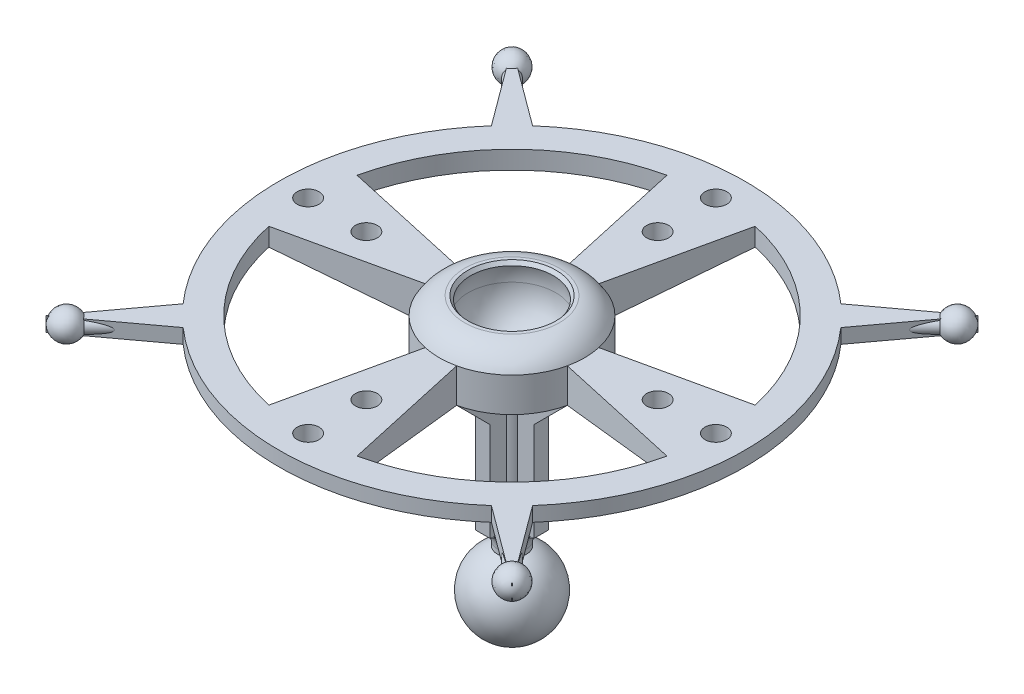
SolidWorks part; units mm, degrees
other "Markup1"
sketch "Sketch8" plane through (-15, -13.5, -15) normal (-0.6433, -0.4106, -0.6463) x (0.1908, 0.7315, -0.6546)
ref_plane "Front Plane" through (0, 0, 0) normal (0, 0, 1) x (1, 0, 0)
ref_plane "Top Plane" through (0, 0, 0) normal (0, 1, 0) x (1, 0, 0)
ref_plane "Right Plane" through (0, 0, 0) normal (1, 0, 0) x (0, 0, -1)
sketch "Sketch1" plane through (0, 0, 0) normal (1, 0, 0) x (0, 0, -1)
  line L0 (0, 4) -> (0, 0) construction
  line L1 (0, 0) -> (0, -9.5)
  line L2 (0, -9.5) -> (0, -12.3) construction
  line L3 (-4, 4) -> (-16, 4)
  line L4 (-16, 4) -> (-16, 3)
  line L5 (-16, 3) -> (-3.048, 1.4097)
  line L6 (-4, 4) -> (-3, 4)
  line L7 (0, 0.127) -> (-1, 0.127) construction
  line L8 (1, 0.127) -> (1, -9.6847) construction
  line L9 (0, -9.6847) -> (-1, -9.6847) construction
  line L10 (-1, 0.127) -> (-1, -9.6847)
  line L11 (0, -15.1) -> (0, -9.5)
  line L12 (0, 1) -> (0, 0)
  line L13 (1, 0.127) -> (0, 0.127) construction
  line L14 (1, -9.6847) -> (0, -9.6847) construction
  line L15 (0, 10.6343) -> (0, 14.716) construction
  arc A0 (-1, -9.6847) -> (0, -15.1) centre (0, -12.3) ccw
  arc A1 (-3.048, 1.4097) -> (-1, 0.127) centre (0, 4) ccw
  arc A2 (-3, 4) -> (0, 1) centre (0, 4) ccw
  arc A3 (0, 0) -> (1, 0.127) centre (0, 4) ccw construction
  arc A4 (0, 1) -> (-3, 4) centre (0, 4) ccw construction
  circle A5 centre (0, 4) radius 3 construction
  arc A6 (1, 0.127) -> (-4, 4) centre (0, 4) ccw construction
  circle A7 centre (0, 4) radius 4 construction
  arc A8 (-1, 0.127) -> (0, 0) centre (0, 4) ccw construction
  arc A9 (0, -15.1) -> (1, -9.6847) centre (0, -12.3) ccw construction
  arc A10 (1, -9.6847) -> (0, -9.5) centre (0, -12.3) ccw construction
  arc A11 (-4, 4) -> (-3.048, 1.4097) centre (0, 4) ccw construction
  arc A12 (0, -9.5) -> (-1, -9.6847) centre (0, -12.3) ccw construction
  point P11 (3.8252, 5.1695)
  point P18 (0, -12.3)
  point P20 (3.5, 4)
  dimension "D1" = 9.5
  dimension "D2" = 4
  dimension "D3" = 2.8
  dimension "D5" = 12
  dimension "D6" = 1
  dimension "D7" = 97
  dimension "D8" = 2
  dimension "D4" = 1
revolve "Revolve1" add sketch "Sketch1" angle 360 about L15 region at (0, -4.75, 0.2492)
sketch "Sketch2" plane through (0, 4, 0) normal (0, 1, 0) x (1, 0, 0)
  line L0 (-16, 0) -> (16, 0) construction
  line L1 (0.014, 16) -> (0.014, -16) construction
  circle A0 centre (0, 0) radius 0.5
  circle A1 centre (-9.5, 0) radius 0.75
  circle A2 centre (1.014, -5.5) radius 0.75
  circle A3 centre (0.014, -9.5) radius 0.75
  circle A4 centre (0.014, 9.5) radius 0.75
  circle A5 centre (9.528, 0) radius 0.75
  circle A6 centre (-5.4855, 1) radius 0.75
  circle A7 centre (-5.4855, -1) radius 0.75
  circle A8 centre (-0.986, -5.5) radius 0.75
  circle A9 centre (5.5135, -1) radius 0.75
  circle A10 centre (5.5135, 1) radius 0.75
  circle A11 centre (1.014, 5.5) radius 0.75
  circle A12 centre (-0.986, 5.5) radius 0.75
  circle A13 centre (0, 0) radius 16 construction
  dimension "D1" = 1
  dimension "D3" = 1.5
  dimension "D6" = 1.5
  dimension "D9" = 1.5
  dimension "D2" = 9.5
  dimension "D4" = 5.5
  dimension "D5" = 9.5
  dimension "D7" = 1
  dimension "D8" = 5.4995
  dimension "D10" = 1
extrude "Cut-Extrude1" [suppressed] cut sketch "Sketch2" against normal blind 30 contours A7 | A1 | A3 | A8 | A2 | A9 | A10 | A5 | A11 | A12 | A4 | A6
sketch "Sketch4" plane through (0, 4, 0) normal (0, 1, 0) x (1, 0, 0)
  line L0 (-14, 0) -> (14, 0) construction
  line L1 (-12.1489, 10.4117) -> (12.1489, 10.4117) construction
  line L2 (-12.1489, 10.4117) -> (-12.1489, -10.4117) construction
  line L3 (-12.1489, -10.4117) -> (12.1489, -10.4117) construction
  line L4 (12.1489, 10.4117) -> (12.1489, -10.4117) construction
  line L5 (0, -10.4117) -> (0, 10.4117) construction
  line L6 (-12.1489, 0) -> (12.1489, 0) construction
  line L7 (0, 13) -> (0, -14) construction
  line L8 (-1.0822, 4.8815) -> (0, 0) construction
  line L9 (1.0822, 4.8815) -> (0, 0) construction
  line L10 (-1.0822, -4.8815) -> (0, 0) construction
  line L11 (1.0822, -4.8815) -> (0, 0) construction
  line L12 (-3.463, 15.6207) -> (-1.0822, 4.8815)
  line L13 (3.463, 15.6207) -> (1.0822, 4.8815)
  line L14 (3.463, -15.6207) -> (1.0822, -4.8815)
  line L15 (-3.463, -15.6207) -> (-1.0822, -4.8815)
  line L16 (4.8815, 1.0822) -> (0, 0) construction
  line L17 (4.8815, -1.0822) -> (0, 0) construction
  line L18 (-4.8815, -1.0822) -> (0, 0) construction
  line L19 (-4.8815, 1.0822) -> (0, 0) construction
  line L20 (4.8815, 1.0822) -> (15.6207, 3.463)
  line L21 (4.8815, -1.0822) -> (15.6207, -3.463)
  line L22 (-4.8815, -1.0822) -> (-15.6207, -3.463)
  line L23 (-4.8815, 1.0822) -> (-15.6207, 3.463)
  circle A0 centre (0, 0) radius 16 construction
  circle A3 centre (0, 0) radius 5
  circle A4 centre (0, 0) radius 3
  circle A5 centre (0, 0) radius 6 construction
  circle A6 centre (0, 0) radius 3 construction
  circle A7 centre (14, 0) radius 0.75
  circle A8 centre (10, 0) radius 0.75
  circle A9 centre (0, 10) radius 0.75
  circle A10 centre (0, 14) radius 0.75
  circle A11 centre (0, -14) radius 0.75
  circle A12 centre (0, -10) radius 0.75
  circle A13 centre (-14, 0) radius 0.75
  circle A14 centre (-10, 0) radius 0.75
  circle A15 centre (0, 0) radius 16
  circle A16 centre (0, 0) radius 14
  point P0 (0, 0)
  point P59 (5.8578, 1.2986)
  dimension "D4" = 12
  dimension "D7" = 1.5
  dimension "D5" = 2
  dimension "D6" = 2
  dimension "D8" = 1.5
  dimension "D9" = 1.5
  dimension "D10" = 1.5
  dimension "D12" = 10
  dimension "D2" = 12.5
  dimension "D3" = 12.5
  dimension "D11" = 14
  dimension "D13" = 10
  dimension "D14" = 14
extrude "Cut-Extrude2" cut sketch "Sketch4" against normal blind 4 contours A3 L12 A16 L23 | A3 L22 A16 L15 | A3 L14 A16 L21 | A3 L20 A16 L13 | A13 | A14 | A9 | A10 | A12 | A11 | A8 | A7 region at (-6.8389, 4, -6.8389) region at (6.8389, 4, -6.8389) region at (-6.8389, 4, 6.8389) region at (6.8389, 4, 6.8389)
sketch "Sketch3" plane through (0, 0, 0) normal (0, 1, 0) x (1, 0, 0)
  line L1 (-0.5, 2) -> (0.5, 2)
  line L2 (-0.5, 2) -> (-0.5, -2)
  line L3 (-0.5, -2) -> (0.5, -2)
  line L4 (0.5, 2) -> (0.5, -2)
  line L5 (0, -2) -> (0, 2) construction
  line L6 (-0.5, 0) -> (0.5, 0) construction
  line L7 (-2, 0.5) -> (2, 0.5)
  line L8 (-2, 0.5) -> (-2, -0.5)
  line L9 (-2, -0.5) -> (2, -0.5)
  line L10 (2, 0.5) -> (2, -0.5)
  line L11 (0, -0.5) -> (0, 0.5) construction
  line L12 (-2, 0) -> (2, 0) construction
  point P0 (0, 0)
  point P6 (0, 0)
  dimension "D1" = 1
  dimension "D2" = 4
  dimension "D3" = 1
  dimension "D4" = 4
extrude "Boss-Extrude1" add sketch "Sketch3" against normal blind 8 and the other way up to surface contours L4 L3 L2 L1 | L9 L10 L7 L8 other way up to face at (0, 4, -3)
sketch "Sketch6" plane through (0, 0, 0) normal (0, 0, 1) x (1, 0, 0)
  line L0 (-4.8815, 1.6494) -> (-2, -1.2321)
  line L1 (-4.8815, 1.6494) -> (4.8815, 1.6494)
  line L2 (-2, 0.5722) -> (-2, -8) construction
  line L3 (0, 1.6494) -> (0, -0.8653) construction
  line L4 (4.8815, 1.6494) -> (2, -1.2321)
  line L5 (-2, -1.2321) -> (2, -1.2321)
  point P5 (0, 1.6494)
  dimension "D1" = 45
extrude "Boss-Extrude3" add sketch "Sketch6" along normal mid plane 1
sketch "Sketch5" plane through (0, 4, 0) normal (0, 1, 0) x (1, 0, 0)
  line L0 (-9.5626, 9.5626) -> (9.5626, -9.5626) construction
  line L1 (11.3137, 11.3137) -> (-11.3137, 11.3137) construction
  line L2 (11.3137, 11.3137) -> (11.3137, -11.3137) construction
  line L3 (11.3137, -11.3137) -> (-11.3137, -11.3137) construction
  line L4 (-11.3137, 11.3137) -> (-11.3137, -11.3137) construction
  line L5 (0, -11.3137) -> (0, 11.3137) construction
  line L6 (11.3137, 0) -> (-11.3137, 0) construction
  line L7 (13.6328, 13.6328) -> (-13.6328, -13.6328) construction
  line L8 (-10.5845, 11.9987) -> (-11.9987, 10.5845)
  line L9 (16, 16) -> (11.9987, 10.5845)
  line L10 (10.5845, 11.9987) -> (16, 16)
  line L11 (10.5845, 11.9987) -> (11.9987, 10.5845)
  line L12 (-28.261, -16) -> (27.3338, -16) construction
  line L13 (-25.98, 16) -> (25.98, 16) construction
  line L14 (-13.6328, 13.6328) -> (13.6328, -13.6328) construction
  line L15 (-16, 16) -> (-11.9987, 10.5845)
  line L16 (-10.5845, 11.9987) -> (-16, 16)
  line L17 (-10.5845, 11.9987) -> (-11.9987, 10.5845)
  line L18 (-9.5626, -9.5626) -> (9.5626, 9.5626) construction
  line L19 (-10.5845, -11.9987) -> (-16, -16)
  line L20 (-16, -16) -> (-11.9987, -10.5845)
  line L21 (-10.5845, -11.9987) -> (-11.9987, -10.5845)
  line L22 (10.5845, -11.9987) -> (16, -16)
  line L23 (16, -16) -> (11.9987, -10.5845)
  line L24 (10.5845, -11.9987) -> (11.9987, -10.5845)
  circle A0 centre (0, 0) radius 16 construction
  circle A1 centre (0, 0) radius 16 construction
  point P2 (0, 0)
  point P6 (0, 0)
  point P11 (0, 0)
  point P16 (0, 16)
  point P29 (-11.2916, 11.2916)
  circle M19 centre (0, 0) radius 16
  dimension "D1" = 32
  dimension "D2" = 45
  dimension "D3" = 2
extrude "Boss-Extrude2" add sketch "Sketch5" against normal blind 1 contours L16 L15 M19 | L10 L9 M19 | L22 L23 M19 | L20 L19 M19 region at (-12.8709, 4, -12.8709) region at (12.8709, 4, -12.8709) region at (-12.8709, 4, 12.8709) region at (12.8709, 4, 12.8709)
pattern_circular "CirPattern1" count 2 every 90 about axis through (0, 4, 0) along (0, -1, 0) of "Boss-Extrude3"
sketch "Sketch7" plane through (0, 0, 0) normal (1, 0, 0) x (0, 0, -1)
  line L0 (0, 3.873) -> (0, -0.127) construction
  line L1 (0, -0.127) -> (0, -8.627) construction
  line L2 (0, -8.627) -> (0, -11.127) construction
  line L3 (-4, 3.873) -> (-15, 3.873) construction
  line L4 (-15, 3.873) -> (-15, 2.873) construction
  line L5 (-15, 2.873) -> (-3.1588, 1.4191) construction
  line L6 (-4, 3.873) -> (-3, 3.873) construction
  line L7 (0, 0) -> (1, 0) construction
  line L8 (-1, 0) -> (-1, -8.8357) construction
  line L9 (0, -8.8357) -> (1, -8.8357) construction
  line L10 (1, 0) -> (1, -8.8357) construction
  line L11 (0, -13.627) -> (0, -8.627) construction
  line L12 (0, 0.873) -> (0, -0.127) construction
  line L13 (-1, 0) -> (0, 0) construction
  line L14 (-1, -8.8357) -> (0, -8.8357) construction
  line L15 (0, 10.0263) -> (0, 14.108) construction
  line L16 (-3, 3.873) -> (0, 3.873)
  line L17 (0, 3.873) -> (0, 0.873)
  arc A0 (1, -8.8357) -> (0, -13.627) centre (0, -11.127) ccw construction
  arc A1 (-3.1588, 1.4191) -> (1, 0) centre (0, 3.873) ccw
  arc A2 (-3, 3.873) -> (0, 0.873) centre (0, 3.873) ccw
  arc A3 (0, -0.127) -> (-1, 0) centre (0, 3.873) ccw construction
  arc A4 (0, 0.873) -> (-3, 3.873) centre (0, 3.873) ccw construction
  arc A5 (-1, 0) -> (-4, 3.873) centre (0, 3.873) ccw construction
  arc A6 (1, 0) -> (0, -0.127) centre (0, 3.873) ccw construction
  arc A7 (0, -13.627) -> (-1, -8.8357) centre (0, -11.127) ccw construction
  arc A8 (-1, -8.8357) -> (0, -8.627) centre (0, -11.127) ccw construction
  arc A9 (-4, 3.873) -> (-3.1588, 1.4191) centre (0, 3.873) ccw construction
  arc A10 (0, -8.627) -> (1, -8.8357) centre (0, -11.127) ccw construction
  point P14 (0, -11.127)
  dimension "D1" = 8.5
  dimension "D2" = 4
  dimension "D3" = 2.5
  dimension "D4" = 11
  dimension "D5" = 1
  dimension "D6" = 97
  dimension "D7" = 2
revolve "Cut-Revolve2" cut sketch "Sketch7" angle 360 about L15 region at (0, 2.5997, 1.2732)
ref_plane "Plane1" through (0, 3.5, 0) normal (0, 1, 0) x (1, 0, 0)
sketch "Sketch9" plane through (0, 3.5, 0) normal (0, 1, 0) x (1, 0, 0)
  line L0 (10.5845, 11.9987) -> (11.9987, 10.5845) construction
  line L1 (11.2916, 11.2916) -> (16, 16)
  line L2 (11.6451, 10.938) -> (15.043, 14.3359)
  line L3 (11.2916, 11.2916) -> (11.6451, 10.938)
  line L4 (16.9164, 16.9164) -> (17.3042, 17.3042) construction
  line L9 (0, 17.5055) -> (0, -17.5055) construction
  line L10 (-7.7081, 0) -> (7.7081, 0) construction
  line L11 (16.9164, -16.9164) -> (17.3042, -17.3042) construction
  line L15 (10.5845, -11.9987) -> (11.9987, -10.5845) construction
  line L19 (11.2916, -11.2916) -> (11.6451, -10.938)
  line L23 (11.6451, -10.938) -> (15.043, -14.3359)
  line L24 (11.2916, -11.2916) -> (16, -16)
  line L25 (-10.5845, -11.9987) -> (-11.9987, -10.5845) construction
  line L26 (-16.9164, -16.9164) -> (-17.3042, -17.3042) construction
  line L27 (-16.9164, 16.9164) -> (-17.3042, 17.3042) construction
  line L28 (-10.5845, 11.9987) -> (-11.9987, 10.5845) construction
  line L29 (-11.2916, -11.2916) -> (-16, -16)
  line L30 (-11.6451, -10.938) -> (-15.043, -14.3359)
  line L31 (-11.2916, -11.2916) -> (-11.6451, -10.938)
  line L32 (-11.2916, 11.2916) -> (-11.6451, 10.938)
  line L33 (-11.6451, 10.938) -> (-15.043, 14.3359)
  line L34 (-11.2916, 11.2916) -> (-16, 16)
  arc A2 (15.043, 14.3359) -> (16, 16) centre (15.2782, 15.3079) ccw
  arc A4 (15.043, -14.3359) -> (16, -16) centre (15.2782, -15.3079) cw
  arc A5 (-15.043, -14.3359) -> (-16, -16) centre (-15.2782, -15.3079) ccw
  arc A7 (-15.043, 14.3359) -> (-16, 16) centre (-15.2782, 15.3079) cw
  point P11 (11.2916, 11.2916)
  point P22 (0, 0)
  point P29 (0, 0)
  dimension "D2" = 1
  dimension "D1" = 0.5
revolve "Revolve2" add sketch "Sketch9" angle 360 about L4
revolve "Revolve3" add sketch "Sketch9<6>" angle 360 about L27
sketch "Sketch9<6>" plane through (0, 3.5, 0) normal (0, 1, 0) x (1, 0, 0) same geometry as "Sketch9"
revolve "Revolve4" add sketch "Sketch9<8>" angle 360 about L26
sketch "Sketch9<8>" plane through (0, 3.5, 0) normal (0, 1, 0) x (1, 0, 0) same geometry as "Sketch9"
revolve "Revolve5" add sketch "Sketch9<9>" angle 360 about L11
sketch "Sketch9<9>" plane through (0, 3.5, 0) normal (0, 1, 0) x (1, 0, 0) same geometry as "Sketch9"
sketch "Sketch10" plane through (0, 4, 0) normal (0, 1, 0) x (1, 0, 0)
  line L0 (-1.0822, 4.8815) -> (1.0822, 4.8815) construction
  line L1 (-1.0822, -4.8815) -> (1.0822, -4.8815) construction
  line L2 (0, -4.8815) -> (0, 4.8815) construction
  point P10 (0, 0)
  point P13 (0, 0)
sketch "Sketch11" plane through (0, 0, 0) normal (1, 0, 0) x (0, 0, -1)
  line L0 (-2.75, 5.199) -> (-3.25, 5.199)
  line L1 (-2.75, 5.199) -> (-2.75, 8.1758) construction
  line L2 (-4.8815, 4) -> (4.8815, 4) construction
  line L3 (0, 3.6803) -> (0, 4.3197) construction
  line L4 (-2.75, 4) -> (-2.75, 5.199) construction
  line L5 (2.75, 5.199) -> (2.75, 8.1758) construction
  line L6 (-3, 4) -> (3, 4) construction
  line L7 (-5, 4) -> (-3, 4)
  line L8 (3, 4) -> (5, 4) construction
  line L9 (-5, 4) -> (-5, 4.5) construction
  line L10 (-5, 4) -> (-4.25, 4) construction
  line L11 (-4.25, 4) -> (-4.25, 4.5) construction
  line L12 (-4.25, 4.5) -> (-5, 4.5) construction
  line L13 (-4.25, 4) -> (-5, 4) construction
  arc A0 (-2.75, 5.199) -> (-3, 4) centre (0, 4) ccw
  arc A1 (-4.9749, 4.5) -> (-5, 4) centre (0, 4) ccw
  arc A2 (5, 4) -> (2.75, 8.1758) centre (0, 4) ccw construction
  arc A3 (2.75, 8.1758) -> (-2.75, 8.1758) centre (0, 4) ccw construction
  circle A4 centre (0, 4) radius 5 construction
  arc A5 (2.75, 5.199) -> (-2.75, 5.199) centre (0, 4) ccw construction
  circle A6 centre (0, 4) radius 3 construction
  arc A7 (-5, 4) -> (5, 4) centre (0, 4) ccw construction
  arc A8 (3, 4) -> (2.75, 5.199) centre (0, 4) ccw construction
  arc A9 (-3, 4) -> (3, 4) centre (0, 4) ccw construction
  arc A10 (-3.25, 5.199) -> (-5, 4) centre (-2.9059, 2.82) ccw
  arc A11 (-2.75, 8.1758) -> (-4.9749, 4.5) centre (0, 4) ccw construction
  point P5 (2.9167, 4.8917)
  point P11 (0, 4)
  point P16 (4.05, 4)
  point P26 (-4.625, 4.5)
  dimension "D1" = 6
  dimension "D2" = 2
  dimension "D5" = 0.5
  dimension "D6" = 0.75
  dimension "D3" = 2.75
  dimension "D4" = 0.5
revolve "Revolve6" add sketch "Sketch11" angle 360 about L3 region at (0, 4.5155, 3.7339)
chamfer "Chamfer1" distance 0.25 angle 60 1 edges at (0, 5.199, -2.75) first distance on face at (0, 3.873, 2.9973)
sketch "Sketch12" plane through (0, 0, 0) normal (1, 0, 0) x (0, 0, -1)
  line L3 (-2.8, -12.3) -> (2.8, -12.3) construction
  line L4 (0, -12.3) -> (0, -1.8178) construction
  line L6 (2, -1.2321) -> (2, -8) construction
  line L7 (0.866, -8) -> (0.866, 0.127) construction
  line L10 (0.6247, -10.0752) -> (0.6177, -8.8454)
  line L11 (0.6177, -8.8454) -> (2, -8.7461)
  line L12 (2, -8.7461) -> (2, -11.3404)
  arc A2 (-1, -9.6847) -> (1, -9.6847) centre (0, -12.3) ccw construction
  arc A3 (2, -10.3404) -> (0.866, -9.6373) centre (0, -12.3) ccw construction
  arc A4 (2.8, -12.3) -> (2, -10.3404) centre (0, -12.3) ccw construction
  arc A5 (-2.8, -12.3) -> (2.8, -12.3) centre (0, -12.3) ccw construction
  arc A6 (0, -9.5) -> (-2.8, -12.3) centre (0, -12.3) ccw construction
  arc A7 (0.866, -9.6373) -> (0, -9.5) centre (0, -12.3) ccw construction
  arc A8 (2, -11.3404) -> (0.6247, -10.0752) centre (-0.2576, -12.4143) ccw
  dimension "D1" = 0.5
  dimension "D2" = 1
sketch "Sketch13" plane through (0, 0, 0) normal (1, 0, 0) x (0, 0, -1)
  line L0 (1, -9.6847) -> (1, -8) construction
  line L1 (1, -9.6847) -> (1, -8)
  line L2 (1, -8) -> (2, -8)
  line L3 (0, -10.7386) -> (0, -12.3) construction
  line L4 (0, -12.3) -> (0, -1.8178) construction
  arc A0 (2, -8) -> (1, -9.6847) centre (2.6563, -9.5287) ccw
revolve "Revolve7" add sketch "Sketch13" angle 360 about L3 region at (0, -8.3465, -1.2752)
chamfer "Chamfer2" distance 0.25 angle 45 4 edges at (-1.4142, -8, 1.4142) (1.4142, -8, 1.4142) (-1.4142, -8, -1.4142) (1.4142, -8, -1.4142) first distance on face at (0, -9.3727, 1)
equation "\"D1@Sketch1\"=16-6.5"
